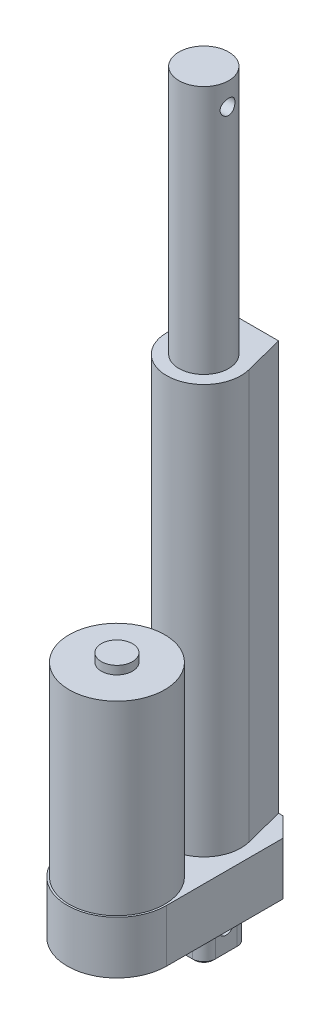
SolidWorks part; units mm, degrees
ref_plane "Front Plane" through (0, 0, 0) normal (0, 0, 1) x (1, 0, 0)
ref_plane "Top Plane" through (0, 0, 0) normal (0, 1, 0) x (1, 0, 0)
ref_plane "Right Plane" through (0, 0, 0) normal (1, 0, 0) x (0, 0, -1)
sketch "Sketch1" plane through (0, 0, 0) normal (0, 1, 0) x (1, 0, 0)
  line L1 (-19.9009, 37.1856) -> (19.9009, 37.1856)
  line L2 (-19.9009, 37.1856) -> (-19.9009, -37.1856)
  line L3 (-19.9009, -37.1856) -> (19.9009, -37.1856)
  line L4 (19.9009, 37.1856) -> (19.9009, -37.1856)
  line L5 (-19.9009, 37.1856) -> (19.9009, -37.1856) construction
  line L6 (-19.9009, -37.1856) -> (19.9009, 37.1856) construction
  point P0 (0, 0)
  dimension "D1" = 39.8018
  dimension "D2" = 74.3712
extrude "Boss-Extrude1 - Shown is a 4 Inch Actuator" add sketch "Sketch1" along normal blind 21.1074
fillet "Fillet1" 2 edges at (19.9009, 10.5537, 37.1856) (-19.9009, 10.5537, 37.1856) type full round first side face at (19.9009, 10.5537, 0) second side face at (-19.9009, 10.5537, 0) middle face at (0, 10.5537, 37.1856)
chamfer "Chamfer1" distance 7.7216 angle 45 2 edges at (19.9009, 10.5537, -37.1856) (-19.9009, 10.5537, -37.1856)
sketch "Sketch2" plane through (0, 21.1074, 0) normal (0, 1, 0) x (1, 0, 0)
  circle A0 centre (0, -17.2847) radius 19.1516
  dimension "D1" = 38.3032
extrude "Boss-Extrude2" add sketch "Sketch2" along normal blind 74.5236
sketch "Sketch3" plane through (0, 95.631, 0) normal (0, 1, 0) x (1, 0, 0)
  circle A0 centre (0, -17.2847) radius 6.2484
  dimension "D1" = 12.4968
extrude "Boss-Extrude3" add sketch "Sketch3" along normal blind 3.3274
sketch "Sketch4" plane through (0, 0, 0) normal (0, -1, 0) x (1, 0, 0)
  line L0 (0, -37.1856) -> (0, -26.5176) construction
  line L1 (-8.9154, -8.6868) -> (8.9154, -8.6868)
  line L2 (-8.9154, -8.6868) -> (-8.9154, -26.5176)
  line L3 (-8.9154, -26.5176) -> (8.9154, -26.5176)
  line L4 (8.9154, -8.6868) -> (8.9154, -26.5176)
  line L5 (-8.9154, -8.6868) -> (8.9154, -26.5176) construction
  line L6 (-8.9154, -26.5176) -> (8.9154, -8.6868) construction
  line L7 (12.1793, -37.1856) -> (-12.1793, -37.1856) construction
  point P0 (0, -17.6022)
  dimension "D1" = 17.8308
  dimension "D2" = 17.8308
  dimension "D3" = 10.668
extrude "Boss-Extrude4" add sketch "Sketch4" along normal blind 19.0246
sketch "Sketch5" plane through (8.9154, 0, 0) normal (1, 0, 0) x (0, 0, -1)
  line L0 (17.6022, -19.0246) -> (17.6022, -12.1412) construction
  line L1 (26.5176, -19.0246) -> (8.6868, -19.0246) construction
  circle A0 centre (17.6022, -9.1694) radius 2.9718
  dimension "D2" = 5.9436
  dimension "D1" = 6.8834
extrude "Cut-Extrude1" cut sketch "Sketch5" against normal through all
fillet "Fillet2" radius 4.572 4 edges at (-8.9154, -9.5123, -26.5176) (-8.9154, -9.5123, -8.6868) (8.9154, -9.5123, -26.5176) (8.9154, -9.5123, -8.6868)
chamfer "Chamfer3" distance 0.762 angle 45 8 edges at (0, -19.0246, -8.6868) (-7.5763, -19.0246, -10.0259) (7.5763, -19.0246, -10.0259) (-8.9154, -19.0246, -17.6022) (8.9154, -19.0246, -17.6022) (-7.5763, -19.0246, -25.1785) (7.5763, -19.0246, -25.1785) (0, -19.0246, -26.5176)
sketch "Sketch6" plane through (0, 21.1074, 0) normal (0, 1, 0) x (1, 0, 0)
  line L0 (0, 37.1856) -> (-10.3378, 37.1856)
  line L1 (12.1793, 37.1856) -> (-12.1793, 37.1856) construction
  line L2 (0, 37.1856) -> (10.3378, 37.1856)
  line L3 (0, 37.1856) -> (0, 27.6098) construction
  line L4 (0, 27.6098) -> (0, 17.5514) construction
  line L5 (-14.4288, 21.2573) -> (-10.3378, 37.1856)
  line L6 (14.4288, 21.2573) -> (10.3378, 37.1856)
  arc A0 (-14.4288, 21.2573) -> (14.4288, 21.2573) centre (0, 17.5514) ccw
  dimension "D5" = 29.7942
  dimension "D1" = 10.3378
  dimension "D2" = 10.3378
  dimension "D3" = 9.5758
  dimension "D4" = 10.0584
extrude "Body Extrude" add sketch "Sketch6" along normal blind 164.0815
sketch "Sketch7" plane through (0, 185.1889, 0) normal (0, 1, 0) x (1, 0, 0)
  circle A0 centre (0, 17.5514) radius 9.9695
  dimension "D1" = 19.939
extrude "Shaft Extrude" add sketch "Sketch7" along normal blind 100
sketch "Sketch8" plane through (0, 0, 0) normal (1, 0, 0) x (0, 0, -1)
  line L0 (17.5514, 285.1889) -> (17.5514, 276.083) construction
  line L1 (27.5209, 285.1889) -> (7.5819, 285.1889) construction
  circle A0 centre (17.5514, 276.083) radius 2.9845
  dimension "D1" = 5.969
  dimension "D2" = 9.1059
extrude "Cut-Extrude2" cut sketch "Sketch8" against normal mid plane 25.4
